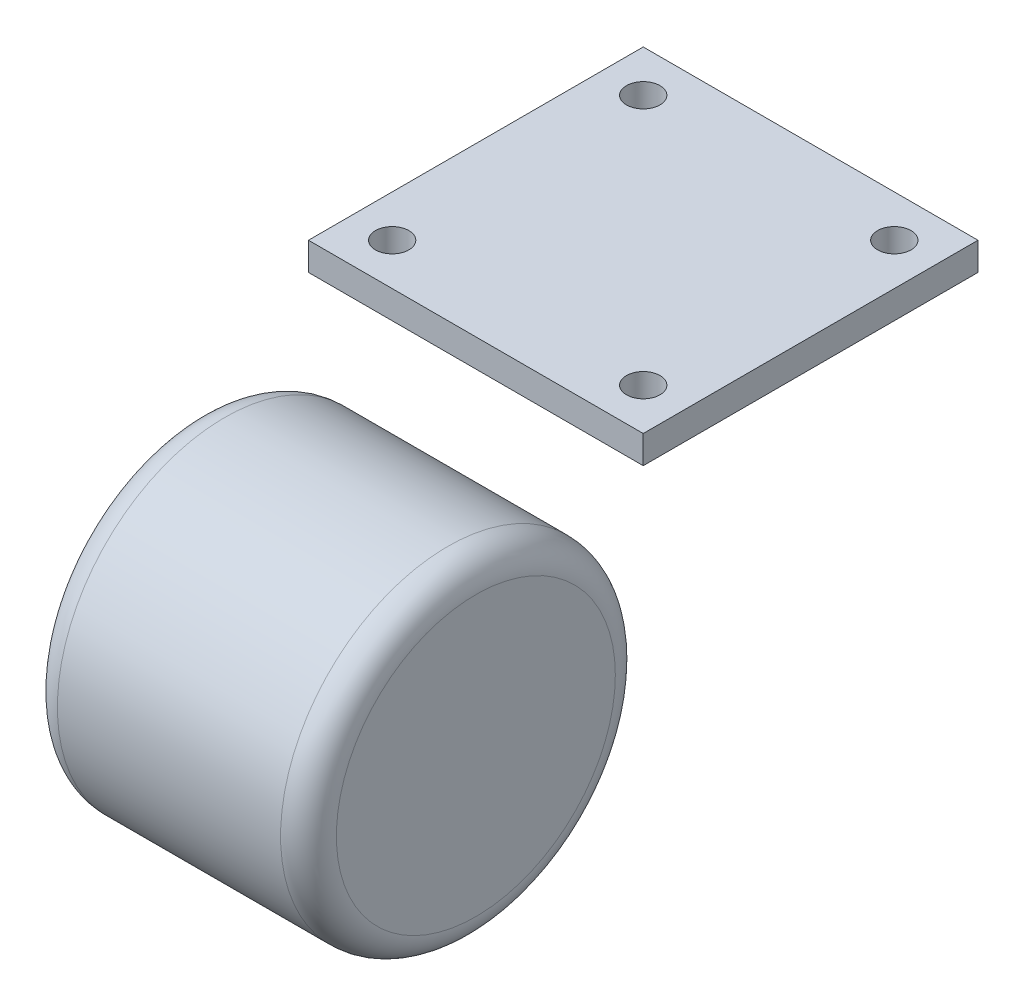
SolidWorks part; units mm, degrees
ref_plane "Front" through (0, 0, 0) normal (0, 0, 1) x (1, 0, 0)
ref_plane "Top" through (0, 0, 0) normal (0, 1, 0) x (1, 0, 0)
ref_plane "Right" through (0, 0, 0) normal (1, 0, 0) x (0, 0, -1)
sketch "Sketch1" plane through (0, 0, 0) normal (0, 1, 0) x (1, 0, 0)
  line L0 (0, 0) -> (0, 52.6463) construction
  line L1 (-30, -30) -> (30, -30)
  line L2 (-30, -30) -> (-30, 30)
  line L3 (-30, 30) -> (30, 30)
  line L4 (30, -30) -> (30, 30)
  line L5 (-30, -30) -> (30, 30) construction
  line L6 (-30, 30) -> (30, -30) construction
  line L7 (0, 0) -> (-64.9392, 0) construction
  line L8 (-26.6814, -85) -> (44.4011, -85) construction
  circle A0 centre (22.5, 22.5) radius 3
  circle A1 centre (-22.5, 22.5) radius 3
  circle A2 centre (22.5, -22.5) radius 3
  circle A3 centre (-22.5, -22.5) radius 3
  point P0 (0, 0)
  dimension "D3" = 6
  dimension "D5" = 45
  dimension "D1" = 60
  dimension "D2" = 60
  dimension "D4" = 115
extrude "Boss-Extrude1" add sketch "Sketch1" along normal blind 5
sketch "Sketch2" plane through (0, 0, 0) normal (1, 0, 0) x (0, 0, -1)
  line L0 (-85, 0) -> (-85, -64.4058) construction
  line L1 (-30, 5) -> (30, 5) construction
  circle A0 centre (-55, -35) radius 30
  dimension "D1" = 60
  dimension "D2" = 70
extrude "Boss-Extrude2" add sketch "Sketch2" along normal mid plane 50 separate body
fillet "Fillet1" radius 5 2 edges at (-25, -35, 25) (25, -35, 25)
ref_axis "Axis1" through (0, 0, 0) along (0, 1, 0)
